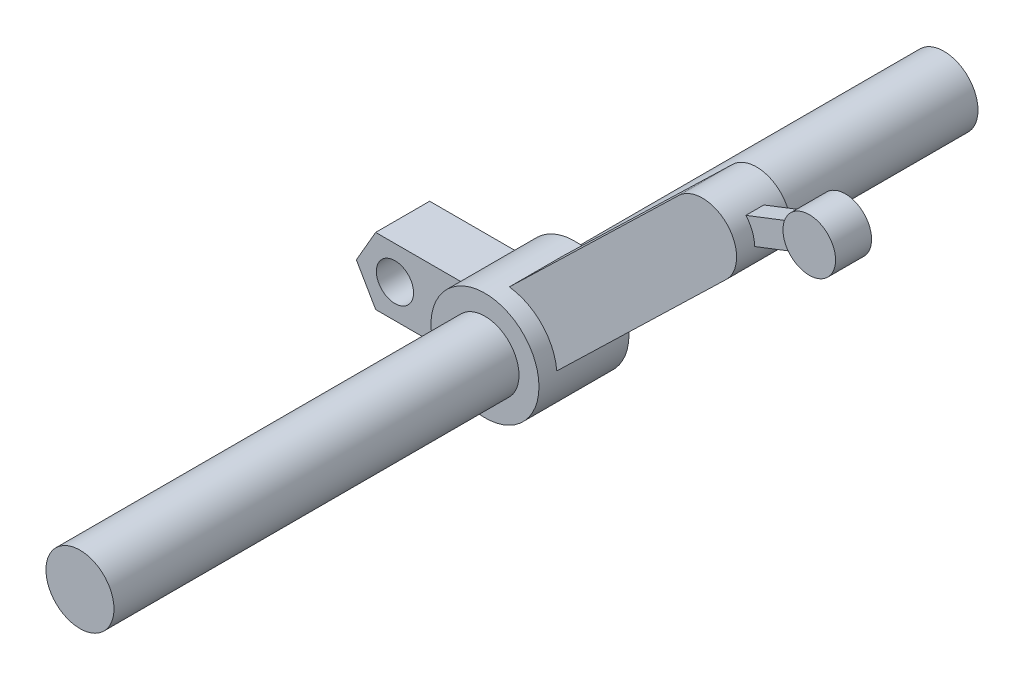
SolidWorks part; units mm, degrees
ref_plane "Ön Düzlem" through (0, 0, 0) normal (0, 0, 1) x (1, 0, 0)
ref_plane "Üst Düzlem" through (0, 0, 0) normal (0, 1, 0) x (1, 0, 0)
ref_plane "Sağ Düzlem" through (0, 0, 0) normal (1, 0, 0) x (0, 0, -1)
sketch "Çizim1" plane through (0, 0, 0) normal (0, 0, 1) x (1, 0, 0)
  circle A0 centre (0, 0) radius 1.89
extrude "Yükseklik-Ekstrüzyon1" add sketch "Çizim1" along normal blind 48
ref_plane "Düzlem1" through (0, 0, 23) normal (0, 0, 1) x (1, 0, 0)
sketch "Çizim2" plane through (0, 0, 23) normal (0, 0, 1) x (1, 0, 0)
  line L0 (0, 1.89) -> (0, -1.8241)
  line L1 (0, 1.89) -> (-6, 1.89)
  line L2 (0, -1.8241) -> (-6, -1.8241)
  line L3 (-6, 1.89) -> (-6, -1.8241)
  line L4 (0, -9.5102) -> (0, 9.5102) construction
  line L6 (-3.8557, 0.033) -> (-4.9278, 1.89)
  line L7 (-4.9278, 1.89) -> (-7.0722, 1.89)
  line L8 (-7.0722, 1.89) -> (-8.1443, 0.033)
  line L9 (-8.1443, 0.033) -> (-7.0722, -1.8241)
  line L10 (-7.0722, -1.8241) -> (-4.9278, -1.8241)
  line L11 (-4.9278, -1.8241) -> (-3.8557, 0.033)
  circle A0 centre (0, 0) radius 3
  circle A1 centre (0, 0) radius 1.89 construction
  circle A2 centre (-6, 0.033) radius 1.857 construction
  point P11 (0, 0)
  point P20 (0, 1.89)
extrude "Yükseklik-Ekstrüzyon2" add sketch "Çizim2" along normal mid plane 5 contours L2 A0 L1 L0 | L1 A0 L2 L0 region at (0.8147, -0.0161, 23) region at (-1.404, 0.0278, 23)
extrude "Yükseklik-Ekstrüzyon3" add sketch "Çizim2<3>" along normal mid plane 3 contours L9 L10 L3 L7 L8 | L1 L3 L2 L0 region at (-6.8339, 0.033, 23)
sketch "Çizim2<3>" plane through (0, 0, 23) normal (0, 0, 1) x (1, 0, 0) same geometry as "Çizim2"
sketch "Çizim6" plane through (0, 0, 23) normal (0, 0, 1) x (1, 0, 0)
  line L0 (0, 0) -> (11.0838, 10.7229) construction
  line L1 (-1.3181, 1.3625) -> (9.7656, 12.0854)
  line L2 (1.3181, -1.3625) -> (12.4019, 9.3604)
  line L3 (11.0838, 10.7229) -> (16.516, 12.8298) construction
  line L4 (10.8402, 11.3509) -> (16.2724, 13.4578)
  line L5 (11.3273, 10.0948) -> (16.7596, 12.2017)
  arc A0 (-1.3181, 1.3625) -> (1.3181, -1.3625) centre (0, 0) ccw
  arc A1 (12.4019, 9.3604) -> (9.7656, 12.0854) centre (11.0838, 10.7229) ccw
  arc A2 (10.8402, 11.3509) -> (11.3273, 10.0948) centre (11.0838, 10.7229) ccw
  arc A3 (16.7596, 12.2017) -> (16.2724, 13.4578) centre (16.516, 12.8298) ccw
  circle A4 centre (16.516, 12.8298) radius 1.4615
  point P3 (5.5419, 5.3614)
  point P8 (13.7999, 11.7763)
  point P17 (8.9261, 6.7122)
  point P18 (14.2314, 9.1491)
  point P19 (9.8145, 9.1745)
  point P20 (14.3583, 11.9921)
  point P21 (11.0838, 10.7229)
  point P22 (16.516, 12.8298)
extrude "Yükseklik-Ekstrüzyon7" add sketch "Çizim6" along normal mid plane 3 contours A2 L4 A1 L1 A0 L2 L5 | L4 A2 L5 A1 region at (5.2448, 5.0912, 23) region at (11.6977, 10.961, 23)
extrude "Yükseklik-Ekstrüzyon8" add sketch "Çizim6<3>" along normal mid plane 1 contours L4 A3 L5 A2
sketch "Çizim6<3>" plane through (0, 0, 23) normal (0, 0, 1) x (1, 0, 0) same geometry as "Çizim6"
extrude "Yükseklik-Ekstrüzyon9" add sketch "Çizim6<4>" along normal mid plane 2 contours A4
sketch "Çizim6<4>" plane through (0, 0, 23) normal (0, 0, 1) x (1, 0, 0) same geometry as "Çizim6"
sketch "Çizim8" plane through (0, 0, 24.5) normal (0, 0, 1) x (1, 0, 0)
  circle A0 centre (-6, 0.033) radius 1.0323
extrude "Kes-Ekstrüzyon1" cut sketch "Çizim8" against normal blind 4
